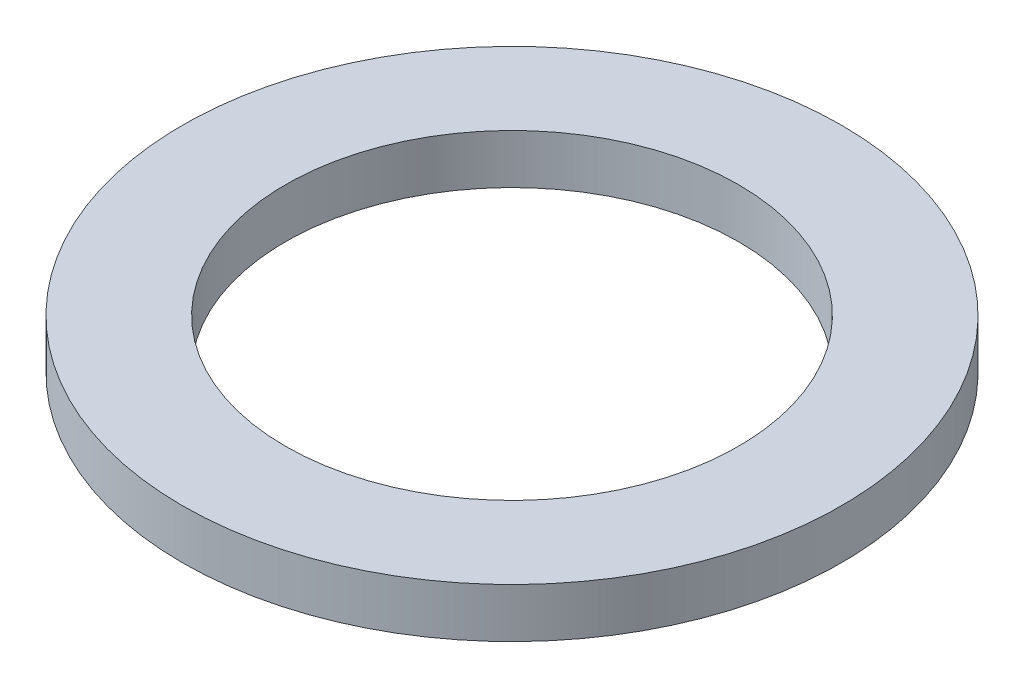
SolidWorks part; units mm, degrees
ref_plane "Front Plane" through (0, 0, 0) normal (0, 0, 1) x (1, 0, 0)
ref_plane "Top Plane" through (0, 0, 0) normal (0, 1, 0) x (1, 0, 0)
ref_plane "Right Plane" through (0, 0, 0) normal (1, 0, 0) x (0, 0, -1)
sketch "Sketch1" plane through (0, 0, 0) normal (0, 1, 0) x (1, 0, 0)
  circle A0 centre (0, 0) radius 40
  dimension "FLANGE_OD" = 80
extrude "Boss-Extrude1" add sketch "Sketch1" along normal blind 6
sketch "Sketch2" plane through (0, 0, 0) normal (0, 1, 0) x (1, 0, 0)
  circle A0 centre (0, 0) radius 27.5
  dimension "BORE_D" = 55
extrude "Cut-Extrude1" cut sketch "Sketch2" along normal through all
sketch "Sketch3" plane through (0, 6, 0) normal (0, 1, 0) x (1, 0, 0)
  circle A0 centre (0, 0) radius 15.532 construction
  circle A1 centre (-15.532, 0) radius 2.0428
  dimension "BOLT_D" = 4.0856
  dimension "BOLT_PCD" = 31.064
extrude "Cut-Extrude2" cut sketch "Sketch3" against normal blind 4.1987 rebuild error yes
pattern_circular "CirPattern1" count 5 over 360 rebuild error yes
